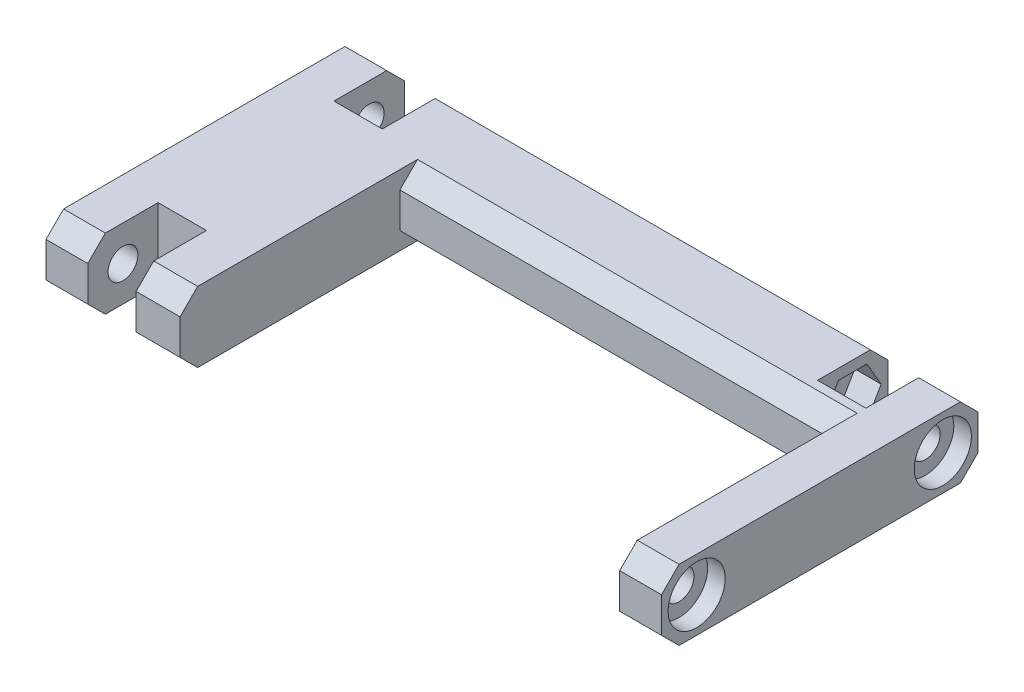
SolidWorks part; units mm, degrees
ref_plane "Front Plane" through (0, 0, 0) normal (0, 0, 1) x (1, 0, 0)
ref_plane "Top Plane" through (0, 0, 0) normal (0, 1, 0) x (1, 0, 0)
ref_plane "Right Plane" through (0, 0, 0) normal (1, 0, 0) x (0, 0, -1)
sketch "Sketch1" plane through (0, 0, 0) normal (0, 1, 0) x (1, 0, 0)
  line L1 (-35, -18) -> (35, -18)
  line L2 (-35, -18) -> (-35, 18)
  line L3 (-35, 18) -> (35, 18)
  line L4 (35, -18) -> (35, 18)
  line L5 (-35, -18) -> (35, 18) construction
  line L6 (-35, 18) -> (35, -18) construction
  point P0 (0, 0)
  dimension "D1" = 70
  dimension "D2" = 36
extrude "Boss-Extrude1" add sketch "Sketch1" along normal blind 8
sketch "Sketch2" plane through (0, 8, 0) normal (0, 1, 0) x (1, 0, 0)
  line L0 (35, 18) -> (-35, 18) construction
  line L1 (-30.25, 18) -> (-24.75, 18)
  line L2 (-30.25, 18) -> (-30.25, 10)
  line L3 (-30.25, 10) -> (-24.75, 10)
  line L4 (-24.75, 18) -> (-24.75, 10)
  line L5 (0, 0) -> (0, 18) construction
  line L6 (24.75, 18) -> (24.75, 10)
  line L7 (30.25, 10) -> (24.75, 10)
  line L8 (30.25, 18) -> (30.25, 10)
  line L9 (30.25, 18) -> (24.75, 18)
  dimension "D1" = 5.5
  dimension "D2" = 8
  dimension "D3" = 49.5
extrude "Cut-Extrude1" cut sketch "Sketch2" against normal through all
hole_wizard "CBORE for M3 Cheese Head Screw1" positions "Sketch7" profile "Sketch8" counterbore size "M3" standard "ISO" end condition up to next
sketch "Sketch7" plane through (35, 0, 0) normal (1, 0, 0) x (0, 0, -1)
  line L0 (-18, 8) -> (18, 8) construction
  line L1 (18, 8) -> (18, 0) construction
  point P0 (14, 4)
  dimension "D1" = 4
  dimension "D2" = 4
sketch "Sketch8" plane through (35, 4, -14) normal (0, 1, 0) x (0, 0, -1)
  line L0 (0, 0) -> (0, 56.75)
  line L1 (0, 56.75) -> (1.7, 56.75)
  line L3 (1.7, 56.75) -> (1.7, 2)
  line L4 (1.7, 2) -> (3.25, 2)
  line L5 (3.25, 2) -> (3.25, 0)
  line L7 (3.25, 0) -> (0, 0)
  line L11 (0, -6.35) -> (0, 107.95) construction
  dimension "Thru Hole Dia." = 3.4
  dimension "Thru Hole Depth" = 56.75
  dimension "C'Bore Dia." = 6.5
  dimension "C'Bore Depth" = 2
sketch "Sketch9" plane through (24.75, 0, 0) normal (1, 0, 0) x (0, 0, -1)
  line L1 (15.6166, 6.8) -> (12.3834, 6.8)
  line L2 (12.3834, 6.8) -> (10.7668, 4)
  line L3 (10.7668, 4) -> (12.3834, 1.2)
  line L4 (12.3834, 1.2) -> (15.6166, 1.2)
  line L5 (15.6166, 1.2) -> (17.2332, 4)
  line L6 (17.2332, 4) -> (15.6166, 6.8)
  circle A0 centre (14, 4) radius 2.8 construction
  dimension "D1" = 5.6
extrude "Cut-Extrude2" cut sketch "Sketch9" against normal blind 3
mirror "Mirror1" about plane through (0, 0, 0) normal (1, 0, 0) of "Cut-Extrude2", "CBORE for M3 Cheese Head Screw1"
mirror "Mirror2" about plane through (0, 0, 0) normal (0, 0, 1) of "Cut-Extrude1", "CBORE for M3 Cheese Head Screw1", "Cut-Extrude2", "Mirror1"
chamfer "Chamfer1" distance 2 angle 45 12 edges at (32.625, 0, -18) (32.625, 8, -18) (0, 0, -18) (0, 8, -18) (-32.625, 0, -18) (-32.625, 8, -18) (-32.625, 0, 18) (32.625, 0, 18) (0, 0, 18) (32.625, 8, 18) (-32.625, 8, 18) (0, 8, 18)
sketch "Sketch10" plane through (0, 8, 0) normal (0, 1, 0) x (1, 0, 0)
  line L0 (24.75, -18) -> (-24.75, -18) construction
  line L1 (-19.75, -18) -> (30.25, -18)
  line L2 (-19.75, -18) -> (-19.75, 7)
  line L3 (-19.75, 7) -> (30.25, 7)
  line L4 (30.25, -18) -> (30.25, 7)
  line L5 (30.25, -10) -> (30.25, -16) construction
  line L6 (-24.75, -10) -> (-24.75, -16) construction
  dimension "D1" = 5
  dimension "D2" = 25
extrude "Cut-Extrude3" cut sketch "Sketch10" against normal through all
chamfer "Chamfer2" distance 2 angle 45 2 edges at (5.25, 0, -7) (5.25, 8, -7)
